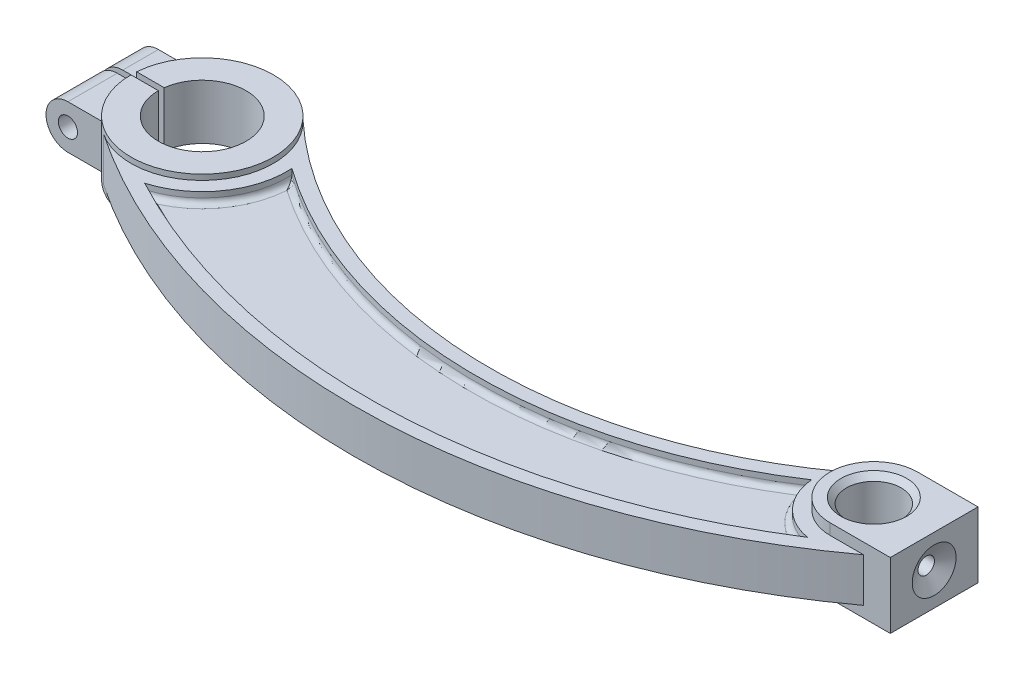
SolidWorks part; units mm, degrees
ref_plane "前视基准面" through (0, 0, 0) normal (0, 0, 1) x (1, 0, 0)
ref_plane "上视基准面" through (0, 0, 0) normal (0, 1, 0) x (1, 0, 0)
ref_plane "右视基准面" through (0, 0, 0) normal (1, 0, 0) x (0, 0, -1)
sketch "草图1" plane through (0, 0, 0) normal (0, 1, 0) x (1, 0, 0)
  circle A0 centre (0, 0) radius 26
  dimension "D1" = 52
extrude "凸台-拉伸1" add sketch "草图1" along normal mid plane 20
sketch "草图2" plane through (0, 0, 0) normal (0, 1, 0) x (1, 0, 0)
  line L0 (245, 0) -> (267, 0) construction
  line L1 (245, 16) -> (267, 16)
  line L2 (245, -16) -> (267, -16)
  line L3 (267, 16) -> (267, -16)
  arc A0 (245, 16) -> (245, -16) centre (245, 0) ccw
  point P3 (256, 0)
  dimension "D1" = 16
  dimension "D2" = 22
  dimension "D3" = 245
extrude "凸台-拉伸2" add sketch "草图2" along normal mid plane 24 separate body
sketch "草图3" plane through (0, 0, 0) normal (0, 1, 0) x (1, 0, 0)
  line L0 (245, -16) -> (267, -16) construction
  line L3 (245, -16) -> (257.2485, -16)
  arc A0 (17.7088, 19.0367) -> (234.8424, 12.3621) centre (130.0918, 139.8468) ccw
  arc A1 (245, 16) -> (245, -16) centre (245, 0) ccw construction
  circle A2 centre (0, 0) radius 26 construction
  arc A3 (234.8424, 12.3621) -> (245, -16) centre (245, 0) ccw
  arc A4 (-14.5368, -21.5565) -> (17.7088, 19.0367) centre (0, 0) ccw
  arc A5 (-14.5368, -21.5565) -> (257.2485, -16) centre (117.4124, 174.1101) ccw
  point P13 (192.0959, 84.8478)
  point P14 (119.2435, 172.8612)
  point P15 (117.4124, 174.1101)
  dimension "D1" = 330
  dimension "D2" = 472
extrude "凸台-拉伸3" add sketch "草图3" along normal mid plane 8
sketch "草图4" plane through (0, 0, 0) normal (0, 1, 0) x (1, 0, 0)
  line L0 (241.5313, -20.7116) -> (241.5313, -20.7116)
  line L1 (257.2485, -16) -> (245, -16)
  line L2 (257.2485, -16) -> (245, -16)
  arc A0 (224.0781, -1.8098) -> (241.5313, -20.7116) centre (245, 0) ccw
  arc A1 (30.9506, 1.7489) -> (224.0781, -1.8098) centre (130.0918, 139.8468) ccw
  arc A2 (8.7535, -29.7385) -> (30.9506, 1.7489) centre (0, 0) ccw
  arc A3 (8.7535, -29.7385) -> (241.5313, -20.7116) centre (117.4124, 174.1101) ccw
  arc A4 (234.8424, 12.3621) -> (245, -16) centre (245, 0) ccw
  arc A5 (17.7088, 19.0367) -> (234.8424, 12.3621) centre (130.0918, 139.8468) ccw
  arc A6 (-14.5368, -21.5565) -> (17.7088, 19.0367) centre (0, 0) ccw
  arc A7 (-14.5368, -21.5565) -> (257.2485, -16) centre (117.4124, 174.1101) ccw
  arc A8 (234.8424, 12.3621) -> (245, -16) centre (245, 0) ccw
  arc A9 (17.7088, 19.0367) -> (234.8424, 12.3621) centre (130.0918, 139.8468) ccw
  arc A10 (-14.5368, -21.5565) -> (17.7088, 19.0367) centre (0, 0) ccw
  arc A11 (-14.5368, -21.5565) -> (257.2485, -16) centre (117.4124, 174.1101) ccw
  dimension "D1" = 0
  dimension "D2" = 5
extrude "凸台-拉伸4" add sketch "草图4" along normal mid plane 16
sketch "草图5" plane through (0, 0, 0) normal (0, 0, 1) x (1, 0, 0)
  line L0 (0, 0) -> (-31, 0) construction
  line L1 (0, -8) -> (-31, -8)
  line L2 (0, 8) -> (-31, 8)
  arc A0 (0, -8) -> (0, 8) centre (0, 0) ccw
  arc A1 (-31, 8) -> (-31, -8) centre (-31, 0) ccw
  point P3 (-15.5, 0)
  dimension "D1" = 16
  dimension "D2" = 31
extrude "凸台-拉伸5" add sketch "草图5" along normal blind 33 from offset 15 offset against normal yes
sketch "草图6" plane through (0, 0, 18) normal (0, 0, 1) x (1, 0, 0)
  circle A0 centre (-31, 0) radius 3.5
  arc A1 (-31, 8) -> (-31, -8) centre (-31, 0) ccw construction
  dimension "D1" = 7
extrude "切除-拉伸1" cut sketch "草图6" against normal through all
sketch "草图7" plane through (0, 10, 0) normal (0, 1, 0) x (1, 0, 0)
  circle A0 centre (0, 0) radius 16
  dimension "D1" = 32
extrude "切除-拉伸2" cut sketch "草图7" against normal through all
sketch "草图8" plane through (0, 0, 0) normal (0, 1, 0) x (1, 0, 0)
  line L1 (0, 0) -> (-47.4792, 0)
  line L2 (0, 0) -> (0, 2)
  line L3 (0, 2) -> (-47.4792, 2)
  line L4 (-47.4792, 0) -> (-47.4792, 2)
  dimension "D1" = 2
extrude "切除-拉伸3" cut sketch "草图8" against normal through all both and the other way through all
sketch "草图9" plane through (0, 12, 0) normal (0, 1, 0) x (1, 0, 0)
  circle A0 centre (245, 0) radius 10
  arc A1 (245, 16) -> (245, -16) centre (245, 0) ccw construction
  dimension "D1" = 20
extrude "切除-拉伸4" cut sketch "草图9" against normal through all
chamfer "倒角1" distance 2 angle 45 2 edges at (245, 12, 10) (245, -12, 10)
fillet "圆角1" radius 2 8 edges at (126.9599, -4, 30.1244) (25.3371, -4, 17.8615) (126.3636, -4, 56.7164) (229.5713, -4, 14.2463) (25.3371, 4, 17.8615) (126.9599, 4, 30.1244) (229.5713, 4, 14.2463) (126.3636, 4, 56.7164)
sketch "草图10" plane through (267, 0, 0) normal (1, 0, 0) x (0, 0, -1)
  point P0 (0, 0)
hole_wizard "Ø6.0mm 暗销孔1" positions "草图10" profile "草图11" hole size "Ø6.0" standard "GB" end condition up to next
sketch "草图11" plane through (267, 0, 0) normal (0, 1, 0) x (0, 0, -1)
  line L0 (0, 0) -> (0, 12)
  line L1 (0, 12) -> (3, 12)
  line L2 (3, 12) -> (3, 2.8868)
  line L3 (3, 2.8868) -> (8, 0)
  line L5 (8, 0) -> (0, 0)
  line L6 (-3, 2.8868) -> (-8, 0) construction
  line L11 (0, -6.35) -> (0, 107.95) construction
  dimension "通孔孔直径" = 6
  dimension "通孔孔深度" = 12
  dimension "近端锥形沉头孔直径" = 16
  dimension "近端锥形沉头孔角度" = 120
